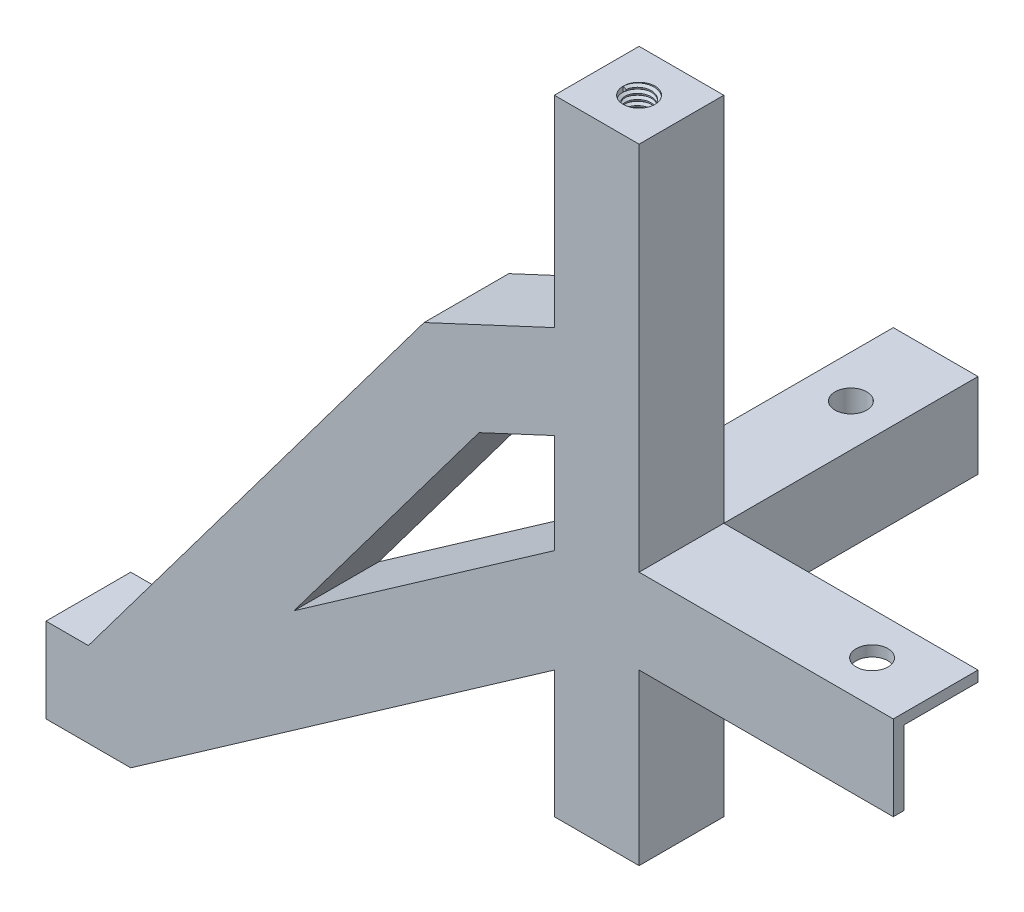
SolidWorks part; units mm, degrees
material "Plain Carbon Steel"
ref_plane "Front Plane" through (0, 0, 0) normal (0, 0, 1) x (1, 0, 0)
ref_plane "Top Plane" through (0, 0, 0) normal (0, 1, 0) x (1, 0, 0)
ref_plane "Right Plane" through (0, 0, 0) normal (1, 0, 0) x (0, 0, -1)
sketch "Sketch1" plane through (0, 0, 0) normal (0, 1, 0) x (1, 0, 0)
  line L1 (12.7, -12.7) -> (-12.7, -12.7)
  line L2 (12.7, -12.7) -> (12.7, 12.7)
  line L3 (12.7, 12.7) -> (-12.7, 12.7)
  line L4 (-12.7, -12.7) -> (-12.7, 12.7)
  line L5 (12.7, -12.7) -> (-12.7, 12.7) construction
  line L6 (12.7, 12.7) -> (-12.7, -12.7) construction
  line L7 (10.16, -10.16) -> (-10.16, -10.16)
  line L8 (10.16, -10.16) -> (10.16, 10.16)
  line L9 (10.16, 10.16) -> (-10.16, 10.16)
  line L10 (-10.16, -10.16) -> (-10.16, 10.16)
  line L11 (10.16, -10.16) -> (-10.16, 10.16) construction
  line L12 (10.16, 10.16) -> (-10.16, -10.16) construction
  point P0 (0, 0)
  point P5 (0, 0)
  dimension "D1" = 2.54
  dimension "1" = 25.4
extrude "Sq_Tb Extrude" add sketch "Sketch1" along normal blind 187.325
sketch "Sketch3" plane through (0, 187.325, 0) normal (0, 1, 0) x (1, 0, 0)
  line L1 (10.16, -10.16) -> (-10.16, -10.16)
  line L2 (10.16, -10.16) -> (10.16, 10.16)
  line L3 (10.16, 10.16) -> (-10.16, 10.16)
  line L4 (-10.16, -10.16) -> (-10.16, 10.16)
  line L5 (10.16, -10.16) -> (-10.16, 10.16) construction
  line L6 (10.16, 10.16) -> (-10.16, -10.16) construction
  circle A0 centre (0, 0) radius 4.7625
  point P0 (0, 0)
  dimension "D1" = 9.525
extrude "End Caps" add sketch "Sketch3" against normal blind 6.35
ref_plane "Mid-Plane" through (0, 93.6625, 0) normal (0, 1, 0) x (1, 0, 0)
mirror "End Cap Mirror" about plane through (0, 93.6625, 0) normal (0, 1, 0) of "End Caps"
thread "Top Thread" pitch 1.5875 method extrude profile "Thread Profile1" start angle 0, offset 0, length 0, pitch 1.5875, diameter 9.525
ref_plane "Plane2" through (-4.7625, 187.325, 0) normal (0, 0, 1) x (-1, 0, 0)
sketch "Thread Profile1" plane through (-4.7625, 187.325, 0) normal (0, 0, 1) x (-1, 0, 0)
  line L0 (0, 0) -> (0, 1.5875) construction
  line L11 (0, 0) -> (0, 1.3891)
  line L12 (0, 1.3891) -> (-0.8593, 0.893)
  line L13 (-0.8593, 0.893) -> (-0.8593, 0.4961)
  line L15 (-0.8593, 0.4961) -> (0, 0)
  line L17 (-0.8593, 0.6945) -> (0, 0.6945) construction
  point P2 (0, 0)
  dimension "Pitch" = 1.5875
  dimension "Profile_Angle" = 60
  dimension "Profile_Land" = 0.3969
  dimension "Profile_Height" = 0.8593
thread "Bottom Thread" pitch 1.5875 method extrude profile "Thread Profile2" start angle 0, offset 0, length 0, pitch 1.5875, diameter 9.525
ref_plane "Plane3" through (4.7625, 0, 0) normal (0, 0, 1) x (1, 0, 0)
sketch "Thread Profile2" plane through (4.7625, 0, 0) normal (0, 0, 1) x (1, 0, 0)
  line L0 (0, 0) -> (0, 1.5875) construction
  line L11 (0, 0) -> (0, 1.3891)
  line L12 (0, 1.3891) -> (-0.8593, 0.893)
  line L13 (-0.8593, 0.893) -> (-0.8593, 0.4961)
  line L15 (-0.8593, 0.4961) -> (0, 0)
  line L17 (-0.8593, 0.6945) -> (0, 0.6945) construction
  point P2 (0, 0)
  dimension "Pitch" = 1.5875
  dimension "Profile_Angle" = 60
  dimension "Profile_Land" = 0.3969
  dimension "Profile_Height" = 0.8593
sketch "Sketch9" plane through (0, 0, 0) normal (0, 0, 1) x (1, 0, 0)
  line L0 (-12.7, 126.996) -> (-51.7653, 108.7796)
  line L1 (-12.7, 187.325) -> (-12.7, 0) construction
  line L2 (-102.0827, 41.6898) -> (-81.7627, 26.4498) construction
  line L3 (-35.2635, 88.4487) -> (-12.7, 98.9702)
  line L4 (-12.7, 38.0909) -> (-139.7, -50.8)
  line L5 (-90.7525, 14.4633) -> (-12.7, 69.0945)
  line L6 (-12.7, 69.0945) -> (-12.7, 38.0909)
  line L8 (-51.7653, 108.7796) -> (-152.4, -25.4)
  line L9 (-12.7, 126.996) -> (-12.7, 98.9702)
  line L10 (-139.7, -50.8) -> (-35.2635, 88.4487)
  line L11 (-139.7, -50.8) -> (-165.1, -50.8)
  line L12 (-165.1, -50.8) -> (-165.1, -25.4)
  line L13 (-165.1, -25.4) -> (-152.4, -25.4)
  line L14 (-32.2327, 117.8878) -> (-21.4982, 94.8676) construction
  line L15 (-165.1, -38.1) -> (0, -38.1) construction
  line L16 (0, -38.1) -> (0, 0) construction
  line L18 (-12.7, 0) -> (12.7, 0) construction
  line L19 (-51.7262, 41.7789) -> (-37.1613, 20.9697) construction
  line L20 (-12.7, 69.0945) -> (32.9312, 3.9003) construction
  line L21 (-139.7, -50.8) -> (-114.9192, -86.2048) construction
  dimension "D3" = 172.7962
  dimension "D1" = 25.4
  dimension "D2" = 43.1038
  dimension "D4" = 65
  dimension "D5" = 12.7
  dimension "D6" = 152.4
  dimension "D7" = 115
  dimension "D8" = 25.4
  dimension "D9" = 50.8
  dimension "D10" = 55.011
  dimension "D11" = 60.329
  dimension "D12" = 38.0909
  dimension "D13" = 88.9052
extrude "Sq_Tb Angles" add sketch "Sketch9" along normal blind 12.7 and the other way blind 12.7 contours L13 L12 L11 L10 L3 L9 L0 L8 | L10 L4 L6 L5
sketch "Sketch11" plane through (0, 0, 0) normal (0, 0, 1) x (1, 0, 0)
  line L0 (-165.1, -38.1) -> (-254, -38.1)
  line L1 (-165.1, -50.8) -> (-165.1, -25.4) construction
  line L2 (-254, -38.1) -> (-254, -28.575)
  line L3 (-254, -28.575) -> (-165.1, -28.575)
  line L6 (-165.1, -28.575) -> (-165.1, -38.1)
  dimension "D2" = 9.525
  dimension "D4" = 88.9
revolve "Wheel Rod" [suppressed] add sketch "Sketch11" angle 360 about L0
thread "Wheel Threads" [suppressed] pitch 1.5875 start angle 0, offset 0, length 25.4, pitch 1.5875, diameter 19.05
ref_plane "Plane4" through (-254, -38.1, -9.525) normal (0, -1, 0) x (0, 0, -1)
sketch "Thread Profile3" plane through (-254, -38.1, -9.525) normal (0, -1, 0) x (0, 0, -1)
  line L0 (0, 0) -> (0, 1.5875) construction
  line L11 (0, 0) -> (0, 1.3891)
  line L12 (0, 1.3891) -> (-0.8593, 0.893)
  line L13 (-0.8593, 0.893) -> (-0.8593, 0.4961)
  line L15 (-0.8593, 0.4961) -> (0, 0)
  line L17 (-0.8593, 0.6945) -> (0, 0.6945) construction
  point P2 (0, 0)
  dimension "Pitch" = 1.5875
  dimension "Profile_Angle" = 60
  dimension "Profile_Land" = 0.3969
  dimension "Profile_Height" = 0.8593
ref_plane "Tie-Rod Mount Plane" through (0, 34.925, 0) normal (0, 1, 0) x (1, 0, 0)
sketch "Sketch15" plane through (0, 34.925, 0) normal (0, 1, 0) x (1, 0, 0)
  line L0 (0, 12.7) -> (12.7, 25.4)
  line L1 (12.7, 12.7) -> (-12.7, 12.7) construction
  line L2 (12.7, 25.4) -> (76.2, 25.4)
  line L3 (0, -12.7) -> (12.7, -25.4)
  line L4 (-12.7, -12.7) -> (12.7, -12.7) construction
  line L5 (0, 12.7) -> (12.7, 12.7)
  line L6 (12.7, -12.7) -> (12.7, 12.7) construction
  line L7 (12.7, 12.7) -> (12.7, -12.7)
  line L8 (12.7, -12.7) -> (0, -12.7)
  line L9 (12.7, -25.4) -> (76.2, -25.4)
  line L10 (76.2, -25.4) -> (76.2, 25.4) construction
  line L11 (12.7, 25.4) -> (12.7, 12.7) construction
  line L12 (12.7, -12.7) -> (12.7, -25.4) construction
  line L13 (76.2, 25.4) -> (88.9, 12.7)
  line L14 (88.9, 12.7) -> (88.9, -12.7)
  line L15 (88.9, -12.7) -> (76.2, -25.4)
  line L16 (12.7, 0) -> (88.9, 0) construction
  dimension "D1" = 12.7
  dimension "D2" = 76.2
  dimension "D3" = 12.7
extrude "Tie-Rod Mount Plate" [suppressed] add sketch "Sketch15" along normal blind 6.35
sketch "Sketch16" [suppressed] plane through (0, 41.275, 0) normal (0, 1, 0) x (1, 0, 0)
  line L0 (12.7, 0) -> (63.5, 0) construction
  line L1 (12.7, -12.7) -> (12.7, 12.7) construction
  line L2 (63.5, 0) -> (63.5, 15.875) construction
  line L3 (12.7, 0) -> (76.2, 0) construction
  circle A0 centre (63.5, 15.875) radius 4.7625
  circle A1 centre (63.5, -15.875) radius 4.7625
  circle A2 centre (76.2, 0) radius 4.7625
  dimension "D1" = 50.8
  dimension "D3" = 9.525
  dimension "D2" = 15.875
  dimension "D4" = 63.5
extrude "Tie-Rod Mount Hole" [suppressed] cut sketch "Sketch16" against normal through all
ref_plane "Plane5" through (0, 50.8, 0) normal (0, -1, 0) x (-1, 0, 0)
sketch "Sketch17" plane through (0, 50.8, 0) normal (0, -1, 0) x (-1, 0, 0)
  line L0 (-12.7, -12.7) -> (-12.7, 12.7) construction
  line L1 (-12.7, 12.7) -> (12.7, 12.7)
  line L2 (-12.7, 12.7) -> (-12.7, 88.9)
  line L3 (-12.7, 88.9) -> (12.7, 88.9)
  line L4 (12.7, 12.7) -> (12.7, 88.9)
  line L5 (-12.7, 12.7) -> (12.7, 88.9) construction
  line L6 (-12.7, 88.9) -> (12.7, 12.7) construction
  line L7 (-12.7, 12.7) -> (12.7, 12.7) construction
  point P4 (0, 50.8)
  dimension "D1" = 25.4
  dimension "D2" = 76.2
extrude "Front Left Steering Drive Arm" add sketch "Sketch17" against normal blind 25.4
sketch "Sketch18" plane through (0, 76.2, 0) normal (0, 1, 0) x (1, 0, 0)
  line L0 (0, 0) -> (0, 63.5) construction
  circle A0 centre (0, 63.5) radius 4.7625
  dimension "D1" = 63.5
  dimension "D2" = 9.525
extrude "Front Left Steering Drive Arm Cole Cutout" cut sketch "Sketch18" against normal through all
sketch "Sketch19" plane through (12.7, 0, 0) normal (1, 0, 0) x (0, 0, -1)
  line L0 (12.7, 76.2) -> (-12.7, 76.2)
  line L1 (-12.7, 187.325) -> (-12.7, 0) construction
  line L2 (-12.7, 76.2) -> (-12.7, 50.8)
  line L3 (-65.0506, 50.8) -> (65.0506, 50.8) construction
  line L4 (-12.7, 50.8) -> (-9.525, 50.8)
  line L5 (-9.525, 50.8) -> (-9.525, 73.025)
  line L6 (-9.525, 73.025) -> (12.7, 73.025)
  line L7 (12.7, 73.025) -> (12.7, 76.2)
  dimension "D1" = 3.175
extrude "Front Left Drag link arm" add sketch "Sketch19" along normal blind 76.2
sketch "Sketch20" plane through (0, 76.2, 0) normal (0, 1, 0) x (1, 0, 0)
  line L0 (50.8, -12.7) -> (50.8, 0) construction
  line L2 (88.9, -12.7) -> (12.7, -12.7) construction
  line L3 (0, 0) -> (31.75, 0) construction
  line L4 (31.75, 0) -> (69.85, 0) construction
  circle A0 centre (69.85, 0) radius 4.7625
  circle A1 centre (31.75, 0) radius 4.7625 construction
  point P8 (50.8, 0)
  dimension "D1" = 31.75
  dimension "D2" = 9.525
  dimension "D3" = 69.85
extrude "Front Left Drag link arm Hole Cutout" cut sketch "Sketch20" against normal through all
sketch "Sketch21" plane through (-165.1, 0, 0) normal (-1, 0, 0) x (0, 0, 1)
  line L0 (-12.7, -38.1) -> (-9.525, -38.1) construction
  line L1 (-9.525, -47.625) -> (9.525, -47.625)
  line L2 (-9.525, -47.625) -> (-9.525, -28.575)
  line L3 (-9.525, -28.575) -> (9.525, -28.575)
  line L4 (9.525, -47.625) -> (9.525, -28.575)
  line L5 (-9.525, -47.625) -> (9.525, -28.575) construction
  line L6 (-9.525, -28.575) -> (9.525, -47.625) construction
  line L7 (-12.7, -50.8) -> (-12.7, -25.4) construction
  line L8 (0, -47.625) -> (0, -50.8) construction
  line L9 (-12.7, -50.8) -> (12.7, -50.8) construction
  point P0 (0, -38.1)
  dimension "D1" = 19.05
extrude "Cut-Extrude1" cut sketch "Sketch21" against normal through all
